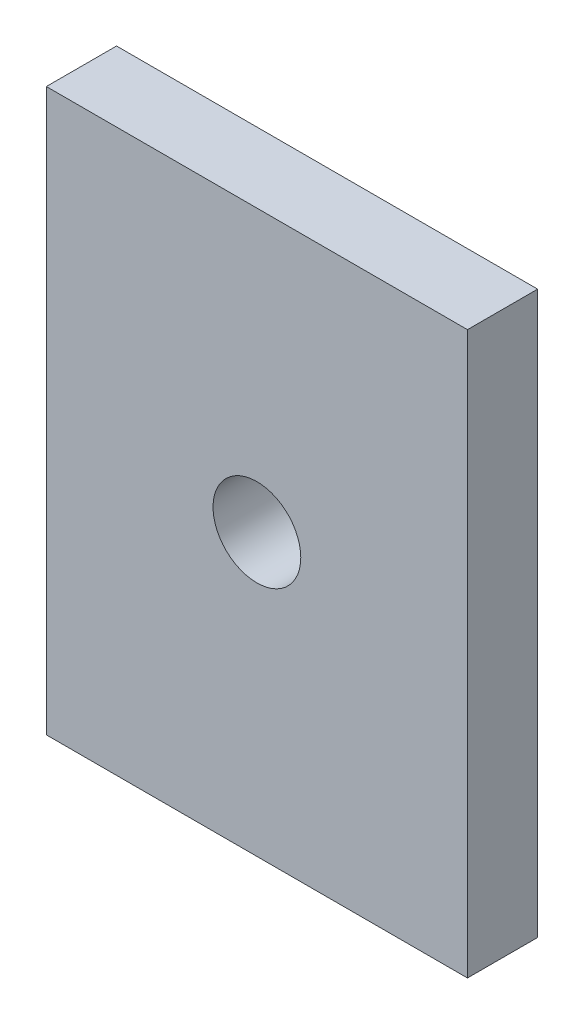
SolidWorks part; units mm, degrees
material "Acrylic (Medium-high impact)"
ref_plane "Front Plane" through (0, 0, 0) normal (0, 0, 1) x (1, 0, 0)
ref_plane "Top Plane" through (0, 0, 0) normal (0, 1, 0) x (1, 0, 0)
ref_plane "Right Plane" through (0, 0, 0) normal (1, 0, 0) x (0, 0, -1)
sketch "Sketch1" plane through (0, 0, 0) normal (0, 0, 1) x (1, 0, 0)
  line L1 (-38.1, 50.8) -> (38.1, 50.8)
  line L2 (-38.1, 50.8) -> (-38.1, -50.8)
  line L3 (-38.1, -50.8) -> (38.1, -50.8)
  line L4 (38.1, 50.8) -> (38.1, -50.8)
  line L5 (-38.1, 50.8) -> (38.1, -50.8) construction
  line L6 (-38.1, -50.8) -> (38.1, 50.8) construction
  circle A0 centre (0, 0) radius 7.9375
  point P0 (0, 0)
  dimension "D3" = 15.875
  dimension "D1" = 76.2
  dimension "D2" = 101.6
extrude "Boss-Extrude1" add sketch "Sketch1" along normal blind 12.7
